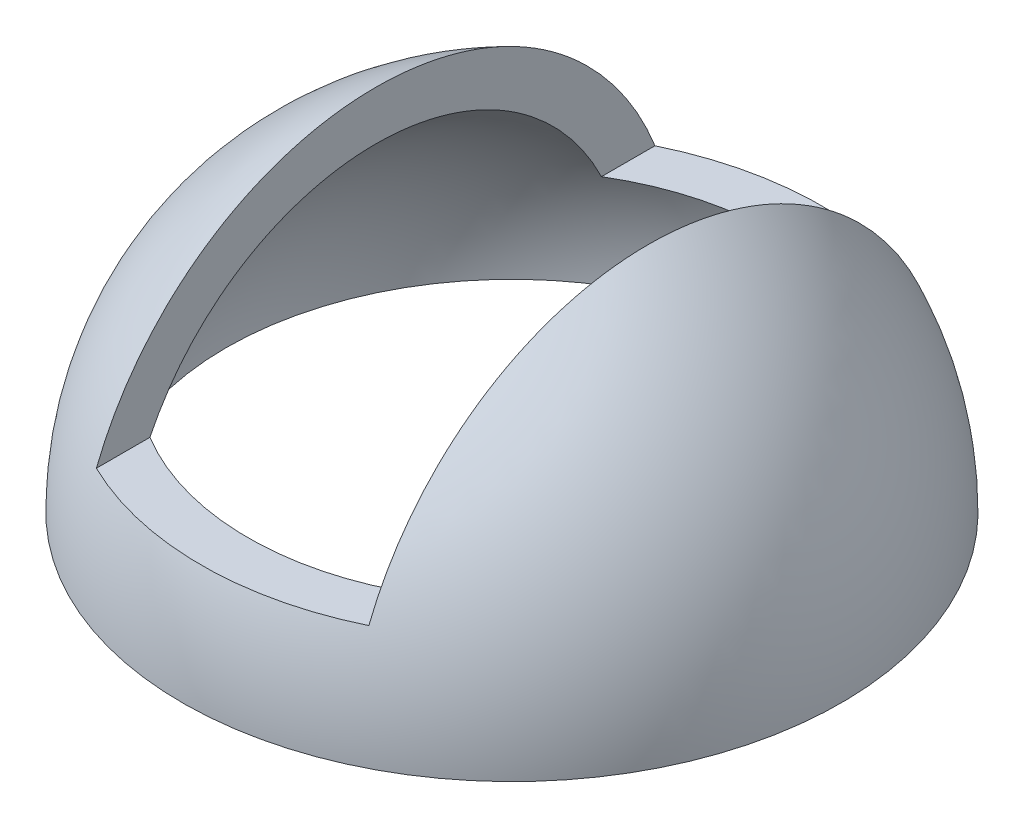
SolidWorks part; units mm, degrees
ref_plane "Front Plane" through (0, 0, 0) normal (0, 0, 1) x (1, 0, 0)
ref_plane "Top Plane" through (0, 0, 0) normal (0, 1, 0) x (1, 0, 0)
ref_plane "Right Plane" through (0, 0, 0) normal (1, 0, 0) x (0, 0, -1)
sketch "Sketch1" plane through (0, 0, 0) normal (0, 0, 1) x (1, 0, 0)
  line L0 (16.51, 0) -> (19.05, 0) construction
  line L1 (19.05, 0) -> (16.51, 0) construction
  line L2 (19.05, 0) -> (16.51, 0)
  line L3 (0, 19.05) -> (0, 16.51)
  arc A0 (19.05, 0) -> (0, 19.05) centre (0, 0) ccw
  arc A2 (16.51, 0) -> (0, 16.51) centre (0, 0) ccw
  circle A3 centre (0, 0) radius 19.05 construction
  circle A4 centre (0, 0) radius 16.51 construction
  dimension "D1" = 38.1
  dimension "D2" = 2.54
revolve "Revolve1" add sketch "Sketch1" angle 360 about L3
sketch "Sketch2" plane through (0, 0, 0) normal (0, 0, 1) x (1, 0, 0)
  line L0 (0, 6.35) -> (0, 0) construction
  line L1 (-7.874, 22.7688) -> (7.874, 22.7688)
  line L2 (-7.874, 22.7688) -> (-7.874, 6.35)
  line L3 (-7.874, 6.35) -> (7.874, 6.35)
  line L4 (7.874, 22.7688) -> (7.874, 6.35)
  dimension "D1" = 6.35
  dimension "D2" = 15.748
extrude "Cut-Extrude1" cut sketch "Sketch2" against normal mid plane 127
